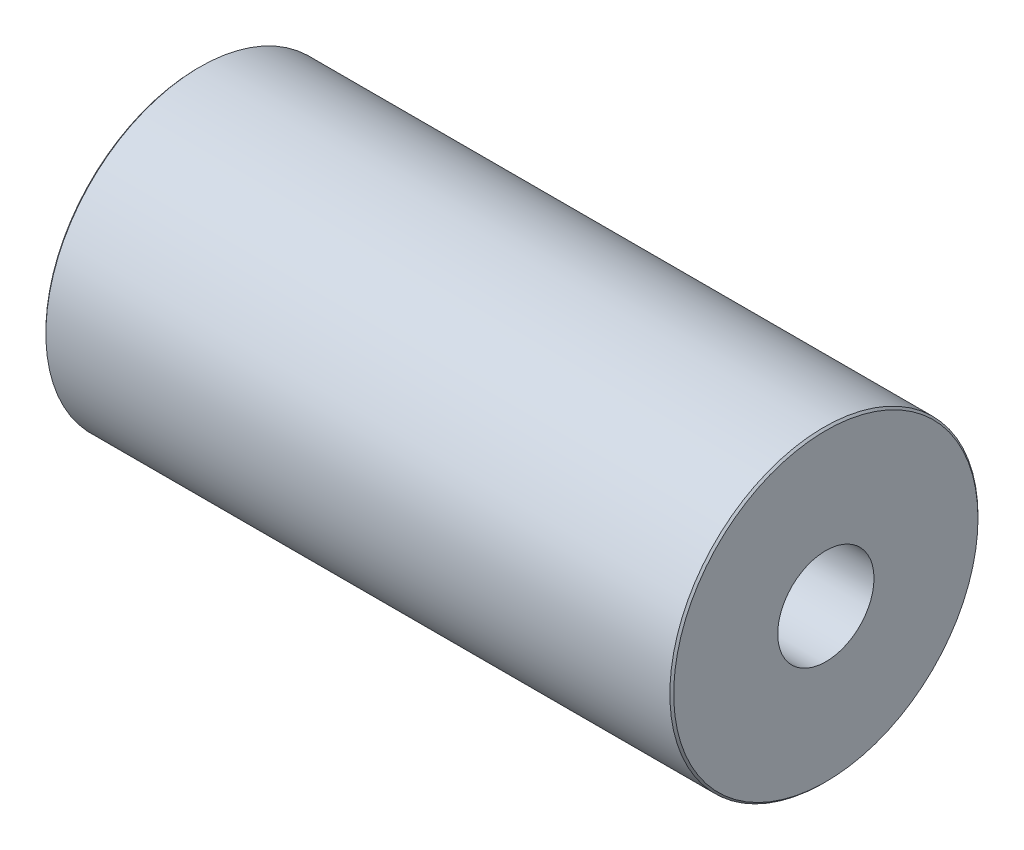
SolidWorks part; units mm, degrees
material "1.7225 (42CrMo4)"
ref_plane "前基準面" through (0, 0, 0) normal (0, 0, 1) x (1, 0, 0)
ref_plane "上基準面" through (0, 0, 0) normal (0, 1, 0) x (1, 0, 0)
ref_plane "右基準面" through (0, 0, 0) normal (1, 0, 0) x (0, 0, -1)
sketch "Sketch1" plane through (0, 0, 0) normal (1, 0, 0) x (0, 0, -1)
  circle A0 centre (0, 0) radius 8
  circle A1 centre (0, 0) radius 3
  dimension "D1" = 6
  dimension "D2" = 16
extrude "Boss-Extrude1" add sketch "Sketch1" along normal mid plane 32.6 contours A1 | A0 A1 region at (0, 0, 7.7737) region at (0, 0, 0)
hole_wizard "M6 Tapped Hole1" positions "Sketch2" profile "Sketch3" tap size "M6" standard "ISO"
sketch "Sketch2" plane through (-16.3, 0, 0) normal (-1, 0, 0) x (0, 0, 1)
  point P0 (0, 0)
sketch "Sketch3" plane through (-16.3, 0, 0) normal (0, 1, 0) x (0, 0, 1)
  line L0 (0, 0) -> (0, 11.5022)
  line L1 (0, 11.5022) -> (2.5, 10)
  line L2 (2.5, 10) -> (2.5, 0)
  line L5 (2.5, 0) -> (0, 0)
  line L10 (0, 11.5022) -> (-2.5, 10) construction
  line L11 (0, -6.35) -> (0, 107.95) construction
  dimension "Tap Drill Dia." = 5
  dimension "Tap Drill Depth" = 10
  dimension "Drill Angle" = 118
cosmetic thread "Hole Thread1" parameters "D1"=12, "D2"=6
mirror "Mirror1" about plane through (0, 0, 0) normal (1, 0, 0) of "M6 Tapped Hole1"
cosmetic thread "Hole Thread2" parameters "D1"=12, "D2"=6
chamfer "Chamfer1" distance 0.1 angle 45 2 edges at (-16.3, 0, -8) (16.3, 0, -8)
